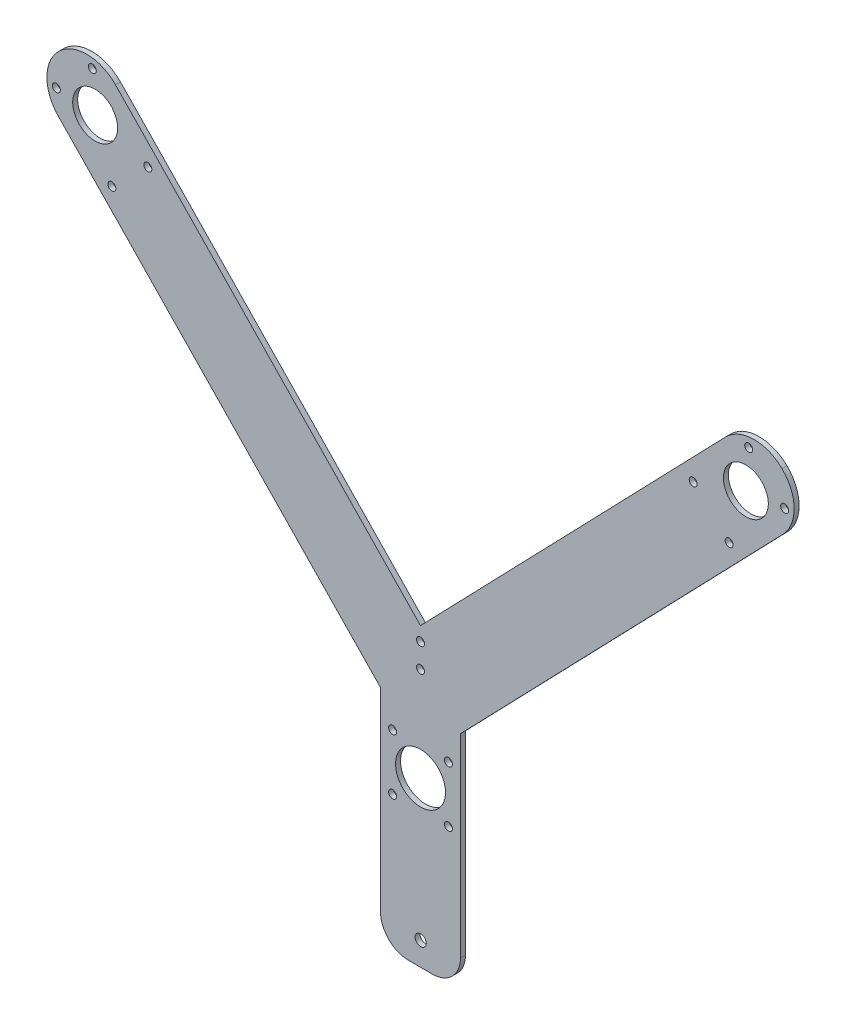
SolidWorks part; units mm, degrees
ref_plane "Front Plane" through (0, 0, 0) normal (0, 0, 1) x (1, 0, 0)
ref_plane "Top Plane" through (0, 0, 0) normal (0, 1, 0) x (1, 0, 0)
ref_plane "Right Plane" through (0, 0, 0) normal (1, 0, 0) x (0, 0, -1)
sketch "Sketch1" plane through (0, 0, 0) normal (0, 0, 1) x (1, 0, 0)
  line L0 (0, 0) -> (50.8, 0)
  line L1 (50.8, 0) -> (50.8, 141.3009)
  line L2 (50.8, 141.3009) -> (273.4748, 371.8874)
  line L3 (0, 0) -> (0, 141.3009)
  line L4 (0, 141.3009) -> (-222.6748, 371.8874)
  line L5 (-222.6748, 371.8874) -> (-186.1323, 407.1761)
  line L6 (-186.1323, 407.1761) -> (25.4, 188.1279)
  line L7 (25.4, 188.1279) -> (236.9323, 407.1761)
  line L8 (236.9323, 407.1761) -> (273.4748, 371.8874)
  circle A0 centre (25.4, 800.087) radius 406.4 construction
  point P3 (-80.3662, 297.652)
  dimension "D1" = 812.8
  dimension "D3" = 50.8
  dimension "D4" = 50.8
  dimension "D5" = 50.8
  dimension "D6" = 88
extrude "Boss-Extrude1" add sketch "Sketch1" along normal blind 3.175 contours L1 L2 L8 L7 L6 L5 L4 L3 L0
sketch "Sketch2" plane through (0, 0, 3.175) normal (0, 0, 1) x (1, 0, 0)
  line L0 (50.8, 141.3009) -> (273.4748, 371.8874) construction
  line L1 (-186.1323, 407.1761) -> (25.4, 188.1279) construction
  line L2 (236.9323, 407.1761) -> (273.4748, 371.8874) construction
  line L3 (-222.6748, 371.8874) -> (-186.1323, 407.1761) construction
  line L4 (50.8, 0) -> (50.8, 141.3009) construction
  line L5 (0, 0) -> (50.8, 0) construction
  line L11 (43.1292, 121.8692) -> (7.6708, 86.4108) construction
  line L12 (43.1292, 86.4108) -> (7.6708, 121.8692) construction
  circle A0 centre (232.2659, 365.7791) radius 14.2875
  circle A1 centre (-181.4659, 365.7791) radius 14.2875
  circle A2 centre (25.4, 104.14) radius 15.875
  circle A3 centre (43.1292, 121.8692) radius 2.54
  circle A4 centre (7.6708, 121.8692) radius 2.54
  circle A5 centre (7.6708, 86.4108) radius 2.54
  circle A6 centre (43.1292, 86.4108) radius 2.54
  dimension "D2" = 28.575
  dimension "D3" = 25.4
  dimension "D4" = 28.575
  dimension "D5" = 33.02
  dimension "D6" = 33.02
  dimension "D8" = 31.75
  dimension "D9" = 104.14
  dimension "D12" = 5.08
  dimension "D13" = 5.08
  dimension "D14" = 5.08
  dimension "D1" = 25.4
  dimension "D7" = 25.4
  dimension "D10" = 35.4584
  dimension "D11" = 35.4584
extrude "Cut-Extrude1" cut sketch "Sketch2" against normal through all
fillet "Fillet1" radius 25.4 4 edges at (273.4748, 371.8874, 1.5875) (236.9323, 407.1761, 1.5875) (-222.6748, 371.8874, 1.5875) (-186.1323, 407.1761, 1.5875)
sketch "Sketch7" plane through (0, 0, 0) normal (0, 0, -1) x (-1, 0, 0)
  circle A0 centre (-25.5077, 14.9496) radius 3.556
  dimension "D1" = 7.112
extrude "Cut-Extrude6" cut sketch "Sketch7" against normal through all contours A0
fillet "Fillet2" radius 17.78 1 edges at (0, 0, 1.5875)
fillet "Fillet3" radius 17.78 1 edges at (50.8, 0, 1.5875)
sketch "Sketch9" plane through (0, 0, 0) normal (0, 0, -1) x (-1, 0, 0)
  line L0 (-256.9187, 368.4549) -> (-221.6301, 331.9124) construction
  line L1 (-221.6301, 331.9124) -> (-198.791, 353.9678) construction
  line L2 (-198.791, 353.9678) -> (-234.0797, 390.5103) construction
  line L3 (-234.0797, 390.5103) -> (-256.9187, 368.4549) construction
  line L4 (-50.8, 141.3009) -> (-255.8305, 353.6162) construction
  line L5 (-232.2659, 365.7791) -> (-216.0423, 381.4462) construction
  circle A2 centre (-234.0797, 390.5103) radius 2.54
  circle A3 centre (-256.9187, 368.4549) radius 2.54
  circle A4 centre (-198.791, 353.9678) radius 2.54
  circle A5 centre (-221.6301, 331.9124) radius 2.54
  dimension "D2" = 50.8
  dimension "D4" = 31.75
  dimension "D5" = 31.75
  dimension "D1" = 19.05
  dimension "D3" = 15.875
extrude "Cut-Extrude7" cut sketch "Sketch9" against normal through all
ref_plane "Plane3" through (25.4, 0, 0) normal (-1, 0, 0) x (0, 0, 1)
mirror "Mirror3" about plane through (25.4, 0, 0) normal (-1, 0, 0) of "Cut-Extrude7"
sketch "Sketch10" plane through (0, 0, 0) normal (0, 0, -1) x (-1, 0, 0)
  line L0 (-25.4, 188.1279) -> (-25.4, 0) construction
  line L1 (-17.78, 0) -> (-33.02, 0) construction
  circle A0 centre (-25.4, 164.0639) radius 2.54
  circle A1 centre (-25.4, 179.3039) radius 2.54
  dimension "D1" = 5.08
  dimension "D2" = 15.24
  dimension "D3" = 15.24
extrude "Cut-Extrude8" cut sketch "Sketch10" against normal through all contours A1 | A0
